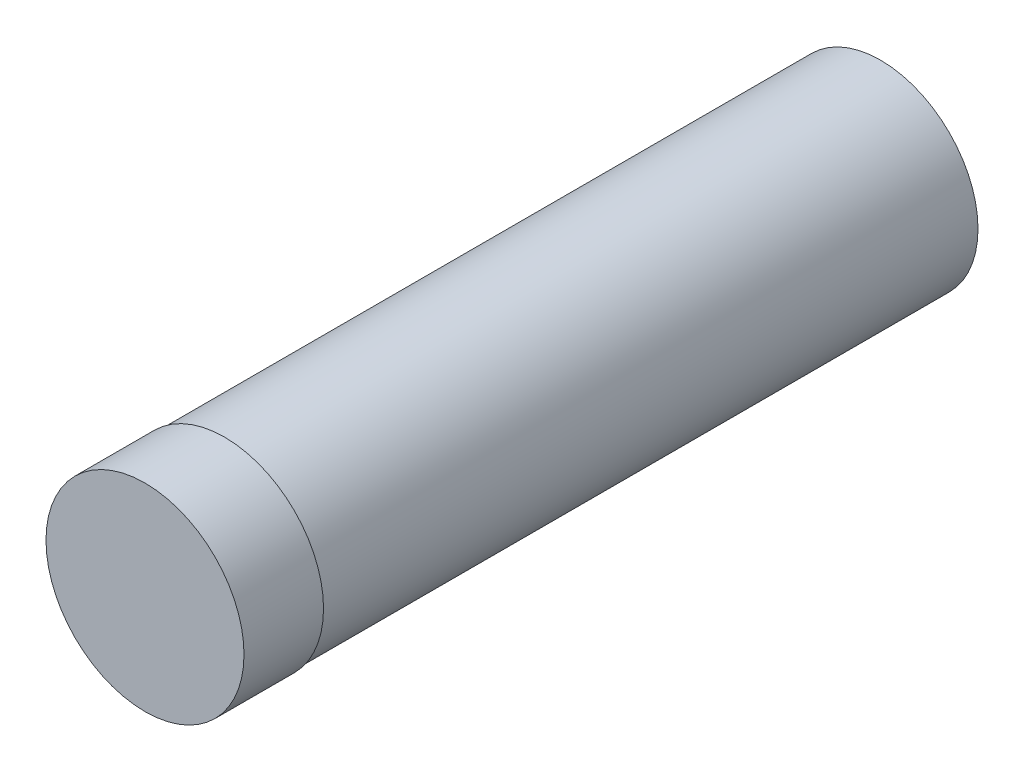
SolidWorks part; units mm, degrees
ref_plane "Front Plane" through (0, 0, 0) normal (0, 0, 1) x (1, 0, 0)
ref_plane "Top Plane" through (0, 0, 0) normal (0, 1, 0) x (1, 0, 0)
ref_plane "Right Plane" through (0, 0, 0) normal (1, 0, 0) x (0, 0, -1)
sketch "Sketch1" plane through (0, 0, 0) normal (0, 0, 1) x (1, 0, 0)
  circle A0 centre (0, 0) radius 2.45
  dimension "D1" = 4.9
extrude "Boss-Extrude1" add sketch "Sketch1" along normal mid plane 18.5
sketch "Sketch2" plane through (0, 0, 0) normal (0, 0, 1) x (1, 0, 0)
  circle A0 centre (0, 0) radius 2.5 construction
  dimension "D1" = 5
sketch "Sketch3" plane through (0, 0, 9.25) normal (0, 0, 1) x (1, 0, 0)
  circle A0 centre (0, 0) radius 2.49
  dimension "D1" = 4.98
extrude "Boss-Extrude2" add sketch "Sketch3" against normal blind 2
